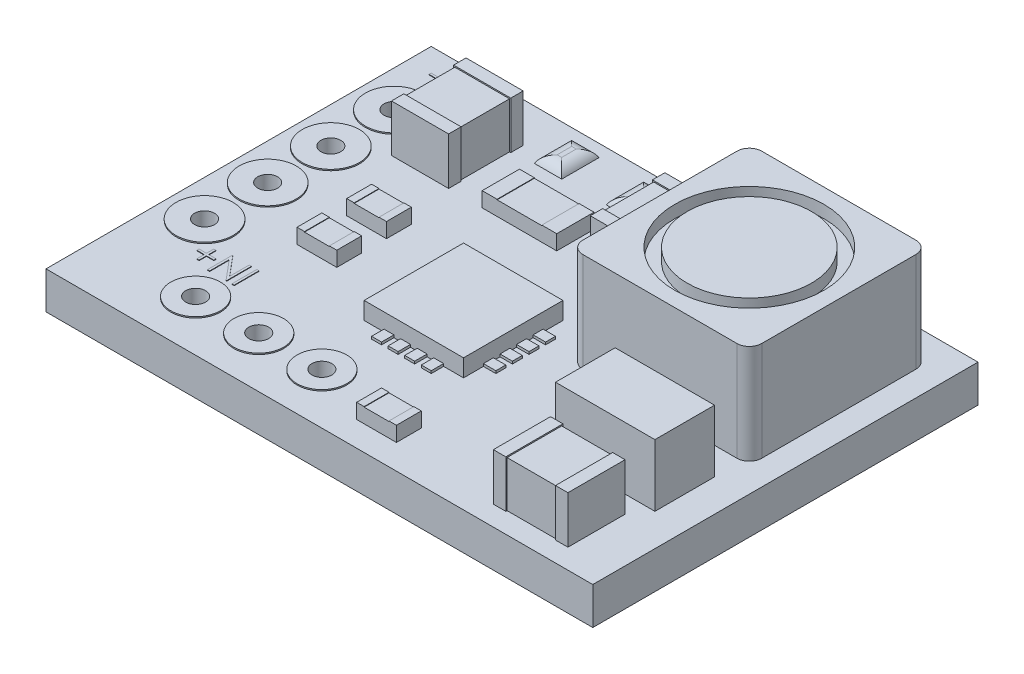
SolidWorks part; units mm, degrees
ref_plane "Přední rovina" through (0, 0, 0) normal (0, 0, 1) x (1, 0, 0)
ref_plane "Horní rovina" through (0, 0, 0) normal (0, 1, 0) x (1, 0, 0)
ref_plane "Pravá rovina" through (0, 0, 0) normal (1, 0, 0) x (0, 0, -1)
sketch "Skica1" plane through (0, 0, 0) normal (0, 1, 0) x (1, 0, 0)
  line L1 (0, 0) -> (22, 0)
  line L2 (0, 0) -> (0, 15.5)
  line L3 (0, 15.5) -> (22, 15.5)
  line L4 (22, 0) -> (22, 15.5)
  dimension "D1" = 22
  dimension "D2" = 15.5
extrude "Přidat vysunutím1" add sketch "Skica1" along normal blind 1.5
sketch "Skica2" plane through (0, 1.5, 0) normal (0, 1, 0) x (1, 0, 0)
  line L0 (22, 15.5) -> (0, 15.5) construction
  line L1 (13.8, 14.5) -> (21, 14.5)
  line L2 (13.8, 14.5) -> (13.8, 7.3)
  line L3 (13.8, 7.3) -> (21, 7.3)
  line L4 (21, 14.5) -> (21, 7.3)
  line L5 (13.8, 14.5) -> (21, 7.3) construction
  line L6 (13.8, 7.3) -> (21, 14.5) construction
  line L7 (22, 0) -> (22, 15.5) construction
  point P0 (17.4, 10.9)
  dimension "D1" = 7.2
  dimension "D2" = 1
  dimension "D3" = 1
extrude "Přidat vysunutím2" add sketch "Skica2" along normal blind 4
fillet "Zaoblit1" radius 0.5 4 edges at (21, 3.5, -14.5) (21, 3.5, -7.3) (13.8, 3.5, -7.3) (13.8, 3.5, -14.5)
sketch "Skica3" plane through (0, 5.5, 0) normal (0, 1, 0) x (1, 0, 0)
  line L0 (13.8, 10.9) -> (21, 10.9) construction
  line L1 (13.8, 14) -> (13.8, 7.8) construction
  line L2 (21, 7.8) -> (21, 14) construction
  circle A0 centre (17.4, 10.9) radius 3
  circle A1 centre (17.4, 10.9) radius 2.5
  dimension "D1" = 6
  dimension "D2" = 5
extrude "Odebrat vysunutím1" cut sketch "Skica3" against normal blind 0.5
sketch "Skica4" plane through (0, 1.5, 0) normal (0, 1, 0) x (1, 0, 0)
  line L0 (22, 0) -> (22, 15.5) construction
  line L1 (20.7, 6.2) -> (16.7, 6.2)
  line L2 (20.7, 6.2) -> (20.7, 3.8)
  line L3 (20.7, 3.8) -> (16.7, 3.8)
  line L4 (16.7, 6.2) -> (16.7, 3.8)
  line L5 (0, 0) -> (22, 0) construction
  dimension "D1" = 4
  dimension "D2" = 2.4
  dimension "D3" = 1.3
  dimension "D4" = 6.2
extrude "Přidat vysunutím3" add sketch "Skica4" along normal blind 2.5
sketch "Skica5" plane through (0, 1.5, 0) normal (0, 1, 0) x (1, 0, 0)
  line L0 (22, 0) -> (22, 15.5) construction
  line L1 (19.7, 3.1) -> (20.2, 3.1)
  line L2 (19.7, 3.1) -> (19.7, 0.8)
  line L3 (19.7, 0.8) -> (20.2, 0.8)
  line L4 (20.2, 3.1) -> (20.2, 0.8)
  line L5 (17.7, 3.1) -> (17.2, 3.1)
  line L6 (17.7, 3.1) -> (17.7, 0.8)
  line L7 (17.7, 0.8) -> (17.2, 0.8)
  line L8 (17.2, 3.1) -> (17.2, 0.8)
  line L9 (0, 0) -> (22, 0) construction
  line L10 (17.7, 3.1) -> (19.7, 3.1) construction
  line L11 (3, 13.9) -> (5.3, 13.9)
  line L12 (3, 13.9) -> (3, 13.4)
  line L13 (3, 13.4) -> (5.3, 13.4)
  line L14 (5.3, 13.9) -> (5.3, 13.4)
  line L15 (3, 11.4) -> (5.3, 11.4)
  line L16 (3, 11.4) -> (3, 10.9)
  line L17 (3, 10.9) -> (5.3, 10.9)
  line L18 (5.3, 11.4) -> (5.3, 10.9)
  line L19 (11, 13.9) -> (13.3, 13.9)
  line L20 (11, 13.9) -> (11, 13.4)
  line L21 (11, 13.4) -> (13.3, 13.4)
  line L22 (13.3, 13.9) -> (13.3, 13.4)
  line L23 (11, 11.4) -> (13.3, 11.4)
  line L24 (11, 11.4) -> (11, 10.9)
  line L25 (11, 10.9) -> (13.3, 10.9)
  line L26 (13.3, 11.4) -> (13.3, 10.9)
  line L27 (11, 13.4) -> (11, 11.4) construction
  line L28 (0, 15.5) -> (0, 0) construction
  line L29 (22, 15.5) -> (0, 15.5) construction
  point P32 (11, 13.65)
  dimension "D1" = 2.3
  dimension "D2" = 3
  dimension "D3" = 0.5
  dimension "D4" = 1.8
  dimension "D5" = 0.8
  dimension "D6" = 3
  dimension "D7" = 1.6
  dimension "D8" = 11
extrude "Přidat vysunutím4" add sketch "Skica5" along normal blind 1.9
sketch "Skica6" plane through (0, 1.5, 0) normal (0, 1, 0) x (1, 0, 0)
  line L0 (17.7, 0.8) -> (17.7, 3.1) construction
  line L1 (17.7, 3.05) -> (19.7, 3.05)
  line L2 (17.7, 3.05) -> (17.7, 0.85)
  line L3 (17.7, 0.85) -> (19.7, 0.85)
  line L4 (19.7, 3.05) -> (19.7, 0.85)
  line L5 (19.7, 3.1) -> (19.7, 0.8) construction
  line L6 (17.7, 0.8) -> (17.7, 3.1) construction
  line L7 (3, 13.4) -> (5.3, 13.4) construction
  line L8 (3.05, 13.4) -> (5.25, 13.4)
  line L9 (3.05, 13.4) -> (3.05, 11.4)
  line L10 (3.05, 11.4) -> (5.25, 11.4)
  line L11 (5.25, 13.4) -> (5.25, 11.4)
  line L12 (5.3, 11.4) -> (3, 11.4) construction
  line L13 (11, 13.4) -> (13.3, 13.4) construction
  line L14 (11.05, 13.4) -> (13.25, 13.4)
  line L15 (11.05, 13.4) -> (11.05, 11.4)
  line L16 (11.05, 11.4) -> (13.25, 11.4)
  line L17 (13.25, 13.4) -> (13.25, 11.4)
  line L18 (13.3, 11.4) -> (11, 11.4) construction
  line L19 (13.3, 11.4) -> (11, 11.4) construction
  line L20 (5.3, 11.4) -> (3, 11.4) construction
  point P8 (17.7, 1.95)
  point P29 (12.15, 11.4)
  point P30 (4.15, 11.4)
  dimension "D1" = 2.2
extrude "Přidat vysunutím5" add sketch "Skica6" along normal offset from surface (1.85 mm away) 0.05 up to face at (17.45, 3.4, -1.95)
sketch "Skica7" plane through (0, 1.5, 0) normal (0, 1, 0) x (1, 0, 0)
  line L0 (22, 0) -> (22, 15.5) construction
  line L1 (8.2, 8.6) -> (12.2, 8.6)
  line L2 (8.2, 8.6) -> (8.2, 4.6)
  line L3 (8.2, 4.6) -> (12.2, 4.6)
  line L4 (12.2, 8.6) -> (12.2, 4.6)
  line L5 (0, 0) -> (22, 0) construction
  dimension "D1" = 9.8
  dimension "D2" = 4.6
  dimension "D3" = 4
extrude "Přidat vysunutím6" add sketch "Skica7" along normal blind 0.7
sketch "Skica8" plane through (0, 1.5, 0) normal (0, 1, 0) x (1, 0, 0)
  line L0 (12.2, 8.6) -> (8.2, 8.6) construction
  line L1 (10.0667, 8.6) -> (9.6667, 8.6)
  line L2 (10.0667, 8.6) -> (10.0667, 9.1)
  line L3 (10.0667, 9.1) -> (9.6667, 9.1)
  line L4 (9.6667, 8.6) -> (9.6667, 9.1)
  line L5 (9.4, 8.6) -> (9.6667, 8.6) construction
  line L6 (9.4, 8.6) -> (9, 8.6)
  line L7 (9.4, 8.6) -> (9.4, 9.1)
  line L8 (9.4, 9.1) -> (9, 9.1)
  line L9 (9, 8.6) -> (9, 9.1)
  line L10 (10.3333, 8.6) -> (10.7333, 8.6)
  line L11 (10.3333, 8.6) -> (10.3333, 9.1)
  line L12 (10.3333, 9.1) -> (10.7333, 9.1)
  line L13 (10.7333, 8.6) -> (10.7333, 9.1)
  line L14 (11, 8.6) -> (11.4, 8.6)
  line L15 (11, 8.6) -> (11, 9.1)
  line L16 (11, 9.1) -> (11.4, 9.1)
  line L17 (11.4, 8.6) -> (11.4, 9.1)
  line L18 (10.0667, 8.6) -> (10.3333, 8.6) construction
  line L19 (10.7333, 8.6) -> (11, 8.6) construction
  line L20 (12.2, 8.6) -> (8.2, 8.6) construction
  point P18 (10.2, 8.6)
  dimension "D1" = 2.4
  dimension "D2" = 0.4
  dimension "D3" = 0.5
extrude "Přidat vysunutím7" add sketch "Skica8" along normal blind 0.1
sketch "Skica9" plane through (0, 1.5, 0) normal (0, 1, 0) x (1, 0, 0)
  line L0 (8.2, 8.6) -> (12.2, 4.6) construction
  circle A0 centre (10.2, 6.6) radius 0.05
  dimension "D1" = 0.1
extrude "Odebrat vysunutím2" cut sketch "Skica9" along normal blind 0.2
pattern_circular "Kruhové pole1" count 4 over 360 about axis through (10.2, 0, -6.6) along (0, 1, 0) of "Přidat vysunutím7"
sketch "Skica11" plane through (0, 1.5, 0) normal (0, 1, 0) x (1, 0, 0)
  line L0 (22, 15.5) -> (0, 15.5) construction
  line L1 (6.15, 15) -> (7.25, 15)
  line L2 (6.15, 15) -> (6.15, 13.5)
  line L3 (6.15, 13.5) -> (7.25, 13.5)
  line L4 (7.25, 15) -> (7.25, 13.5)
  line L5 (9.05, 15) -> (10.15, 15)
  line L6 (9.05, 15) -> (9.05, 13.5)
  line L7 (9.05, 13.5) -> (10.15, 13.5)
  line L8 (10.15, 15) -> (10.15, 13.5)
  line L9 (5.25, 12.4) -> (11.05, 12.4) construction
  line L10 (5.25, 13.4) -> (5.25, 11.4) construction
  line L11 (11.05, 13.4) -> (11.05, 11.4) construction
  line L13 (9.05, 13.5) -> (7.25, 13.5) construction
  line L14 (8.15, 12.4) -> (8.15, 13.5) construction
  dimension "D1" = 1.1
  dimension "D2" = 1.5
  dimension "D3" = 0.5
  dimension "D4" = 1.8
extrude "Přidat vysunutím8" add sketch "Skica11" along normal blind 0.3
fillet "Zaoblit2" radius 0.5 8 edges at (9.6, 1.8, -15) (10.15, 1.8, -14.25) (9.6, 1.8, -13.5) (9.05, 1.8, -14.25) (6.7, 1.8, -15) (7.25, 1.8, -14.25) (6.7, 1.8, -13.5) (6.15, 1.8, -14.25)
sketch "Skica12" plane through (0, 1.5, 0) normal (0, 1, 0) x (1, 0, 0)
  line L0 (7.25, 11.65) -> (9.05, 11.65) construction
  line L1 (6.65, 12.4) -> (7.25, 12.4)
  line L2 (6.65, 12.4) -> (6.65, 10.9)
  line L3 (6.65, 10.9) -> (7.25, 10.9)
  line L4 (7.25, 12.4) -> (7.25, 10.9)
  line L5 (9.05, 12.4) -> (9.65, 12.4)
  line L6 (9.05, 12.4) -> (9.05, 10.9)
  line L7 (9.05, 10.9) -> (9.65, 10.9)
  line L8 (9.65, 12.4) -> (9.65, 10.9)
  line L9 (5.25, 12.4) -> (11.05, 12.4) construction
  line L10 (5.25, 13.4) -> (5.25, 11.4) construction
  line L11 (11.05, 13.4) -> (11.05, 11.4) construction
  line L12 (11, 10.9) -> (13.3, 10.9) construction
  line L13 (8.15, 11.65) -> (8.15, 12.4) construction
  point P16 (0, 0)
  point P19 (8.15, 12.3797)
  point P20 (8.15, 10.9637)
  point P21 (8.15, 12.3045)
  dimension "D1" = 3
  dimension "D2" = 1.5
  dimension "D3" = 0.6
extrude "Přidat vysunutím9" add sketch "Skica12" along normal blind 0.6
sketch "Skica13" plane through (0, 1.5, 0) normal (0, 1, 0) x (1, 0, 0)
  line L0 (7.25, 10.9) -> (7.25, 12.4) construction
  line L1 (7.25, 12.4) -> (9.05, 12.4)
  line L2 (7.25, 12.4) -> (7.25, 10.9)
  line L3 (7.25, 10.9) -> (9.05, 10.9)
  line L4 (9.05, 12.4) -> (9.05, 10.9)
  line L5 (9.05, 12.4) -> (9.05, 10.9) construction
  line L6 (7.25, 10.9) -> (7.25, 12.4) construction
  line L7 (6.65, 10.9) -> (7.25, 10.9) construction
  point P8 (7.25, 11.65)
extrude "Přidat vysunutím10" add sketch "Skica13" along normal offset from surface (0.58 mm away) 0.02 up to face at (6.95, 2.1, -11.65)
sketch "Skica14" plane through (0, 1.5, 0) normal (0, 1, 0) x (1, 0, 0)
  line L0 (4.02, 2) -> (6.56, 2) construction
  line L1 (6.56, 2) -> (9.1, 2) construction
  line L3 (22, 0) -> (22, 15.5) construction
  line L4 (0, 0) -> (22, 0) construction
  circle A0 centre (4.02, 2) radius 0.4
  circle A1 centre (6.56, 2) radius 0.4
  circle A2 centre (9.1, 2) radius 0.4
  dimension "D4" = 0.8
  dimension "D1" = 2.54
  dimension "D2" = 12.9
  dimension "D3" = 2
extrude "Odebrat vysunutím3" cut sketch "Skica14" against normal through all
sketch "Skica15" plane through (0, 1.5, 0) normal (0, 1, 0) x (1, 0, 0)
  circle A0 centre (4.02, 2) radius 1
  circle A1 centre (4.02, 2) radius 0.4
  circle A2 centre (6.56, 2) radius 0.4
  circle A3 centre (6.56, 2) radius 1
  circle A4 centre (9.1, 2) radius 0.4
  circle A5 centre (9.1, 2) radius 1
  circle A6 centre (4.02, 2) radius 0.4 construction
  dimension "D1" = 2
extrude "Přidat vysunutím11" add sketch "Skica15" along normal blind 0.05 and the other way offset from surface (1.55 mm away) 0.05 other way up to face at (4.02, 0, -1.6)
sketch "Skica17" plane through (0, 1.5, 0) normal (0, 1, 0) x (1, 0, 0)
  line L0 (0, 15.5) -> (0, 0) construction
  line L1 (22, 15.5) -> (0, 15.5) construction
  circle A0 centre (1.5, 12.5) radius 0.4
  circle A1 centre (4.02, 2) radius 0.4 construction
  dimension "D1" = 1.5
  dimension "D2" = 3
extrude "Odebrat vysunutím4" cut sketch "Skica17" against normal through all
sketch "Skica18" plane through (0, 1.5, 0) normal (0, 1, 0) x (1, 0, 0)
  circle A0 centre (1.5, 12.5) radius 0.4
  circle A1 centre (1.5, 12.5) radius 1.15
  circle A2 centre (1.5, 12.5) radius 0.4 construction
  dimension "D1" = 2.3
extrude "Přidat vysunutím13" add sketch "Skica18" along normal up to surface and the other way up to surface up to face at (4.02, 1.55, -1) other way up to face at (4.02, -0.05, -3)
pattern_linear "LinPole1" count 4 spacing 2.54 along (0, 0, 1) of "Odebrat vysunutím4", "Přidat vysunutím13"
sketch "Skica20" plane through (-4.5062, 1.5, 3.6547) normal (0, 1, 0) x (1, 0, 0)
  line L0 (9.0062, 12.0547) -> (10.0062, 12.0547) construction
  line L1 (8.7062, 12.5547) -> (9.0062, 12.5547)
  line L2 (8.7062, 12.5547) -> (8.7062, 11.5547)
  line L3 (8.7062, 11.5547) -> (9.0062, 11.5547)
  line L4 (9.0062, 12.5547) -> (9.0062, 11.5547)
  line L5 (10.0062, 12.5547) -> (10.3062, 12.5547)
  line L6 (10.0062, 12.5547) -> (10.0062, 11.5547)
  line L7 (10.0062, 11.5547) -> (10.3062, 11.5547)
  line L8 (10.3062, 12.5547) -> (10.3062, 11.5547)
  line L13 (4.5062, 3.6547) -> (26.5062, 3.6547) construction
  line L15 (9.8062, 14.5547) -> (9.8062, 15.0547) construction
  dimension "D1" = 1.6
  dimension "D2" = 1
  dimension "D3" = 0.3
  dimension "D4" = 8.4
  dimension "D5" = 0.5
extrude "Přidat vysunutím14" add sketch "Skica20" along normal blind 0.6
sketch "Skica22" plane through (-4.5062, 1.5, 3.6547) normal (0, 1, 0) x (1, 0, 0)
  line L0 (9.0062, 11.5547) -> (9.0062, 12.5547) construction
  line L1 (9.0062, 12.5547) -> (10.0062, 12.5547)
  line L2 (9.0062, 12.5547) -> (9.0062, 11.5547)
  line L3 (9.0062, 11.5547) -> (10.0062, 11.5547)
  line L4 (10.0062, 12.5547) -> (10.0062, 11.5547)
  line L5 (10.0062, 12.5547) -> (10.0062, 11.5547) construction
  line L6 (9.0062, 11.5547) -> (9.0062, 12.5547) construction
  line L7 (8.7062, 11.5547) -> (9.0062, 11.5547) construction
  point P8 (9.0062, 12.0547)
extrude "Přidat vysunutím15" add sketch "Skica22" along normal offset from surface (0.58 mm away) 0.02 up to face at (4.35, 2.1, -8.4)
pattern_linear "LinPole2" count 2 spacing 2 along (0, 0, 1) of "Přidat vysunutím14", "Přidat vysunutím15"
sketch "Skica24" plane through (2.4754, 1.5, 8.8232) normal (0, 1, 0) x (1, 0, 0)
  line L0 (9.3246, 10.3232) -> (10.3246, 10.3232) construction
  line L1 (9.0246, 10.8232) -> (9.3246, 10.8232)
  line L2 (9.0246, 10.8232) -> (9.0246, 9.8232)
  line L3 (9.0246, 9.8232) -> (9.3246, 9.8232)
  line L4 (9.3246, 10.8232) -> (9.3246, 9.8232)
  line L5 (10.3246, 10.8232) -> (10.6246, 10.8232)
  line L6 (10.3246, 10.8232) -> (10.3246, 9.8232)
  line L7 (10.3246, 9.8232) -> (10.6246, 9.8232)
  line L8 (10.6246, 10.8232) -> (10.6246, 9.8232)
  line L9 (11.3246, 22.8232) -> (11.3246, 16.6232) construction
  line L10 (14.7246, 9.6232) -> (15.2246, 9.6232) construction
  dimension "D1" = 1.6
  dimension "D2" = 1
  dimension "D3" = 0.3
  dimension "D4" = 0.7
  dimension "D5" = 0.2
extrude "Přidat vysunutím16" add sketch "Skica24" along normal blind 0.6
sketch "Skica26" plane through (2.4754, 1.5, 8.8232) normal (0, 1, 0) x (1, 0, 0)
  line L0 (9.3246, 9.8232) -> (9.3246, 10.8232) construction
  line L1 (9.3246, 10.8232) -> (10.3246, 10.8232)
  line L2 (9.3246, 10.8232) -> (9.3246, 9.8232)
  line L3 (9.3246, 9.8232) -> (10.3246, 9.8232)
  line L4 (10.3246, 10.8232) -> (10.3246, 9.8232)
  line L5 (10.3246, 10.8232) -> (10.3246, 9.8232) construction
  line L6 (9.3246, 9.8232) -> (9.3246, 10.8232) construction
  line L7 (9.0246, 9.8232) -> (9.3246, 9.8232) construction
  point P8 (9.3246, 10.3232)
extrude "Přidat vysunutím17" add sketch "Skica26" along normal offset from surface (0.58 mm away) 0.02 up to face at (11.65, 2.1, -1.5)
sketch "Skica27" plane through (0, 1.5, 0) normal (0, 1, 0) x (1, 0, 0)
  line L0 (2.5, 15) -> (0.6649, 15) construction
  line L1 (22, 15.5) -> (0, 15.5) construction
  line L2 (0, 15.5) -> (0, 0) construction
  line L3 (4.5, 4.2) -> (2.5, 4.2) construction
  line L4 (0, 0) -> (22, 0) construction
  text T0 "B+" font "Century Gothic" height 1
  text T1 "IN+" font "Century Gothic" height 1
  point P3 (2.9025, 4.0766)
  point P4 (4.4414, 4.0568)
  point P11 (2.5, 4.1026)
  point P12 (0, 0)
  point P13 (0, 0)
  point P14 (0, 0)
  dimension "D1" = 0.5
  dimension "D2" = 2.5
  dimension "D3" = 4.2
  dimension "D4" = 4.5
extrude "Přidat vysunutím18" add sketch "Skica27" along normal blind 0.02
sketch "Skica28" plane through (0, 0, 0) normal (0, -1, 0) x (1, 0, 0)
  line L0 (22, 0) -> (22, -15.5) construction
  line L1 (4.5, -5) -> (21.5, -5)
  line L2 (4.5, -5) -> (4.5, -15)
  line L3 (4.5, -15) -> (21.5, -15)
  line L4 (21.5, -5) -> (21.5, -15)
  line L5 (22, -15.5) -> (0, -15.5) construction
  dimension "D1" = 0.5
  dimension "D2" = 0.5
  dimension "D3" = 10
  dimension "D4" = 17
extrude "Přidat vysunutím19" add sketch "Skica28" along normal blind 0.05
